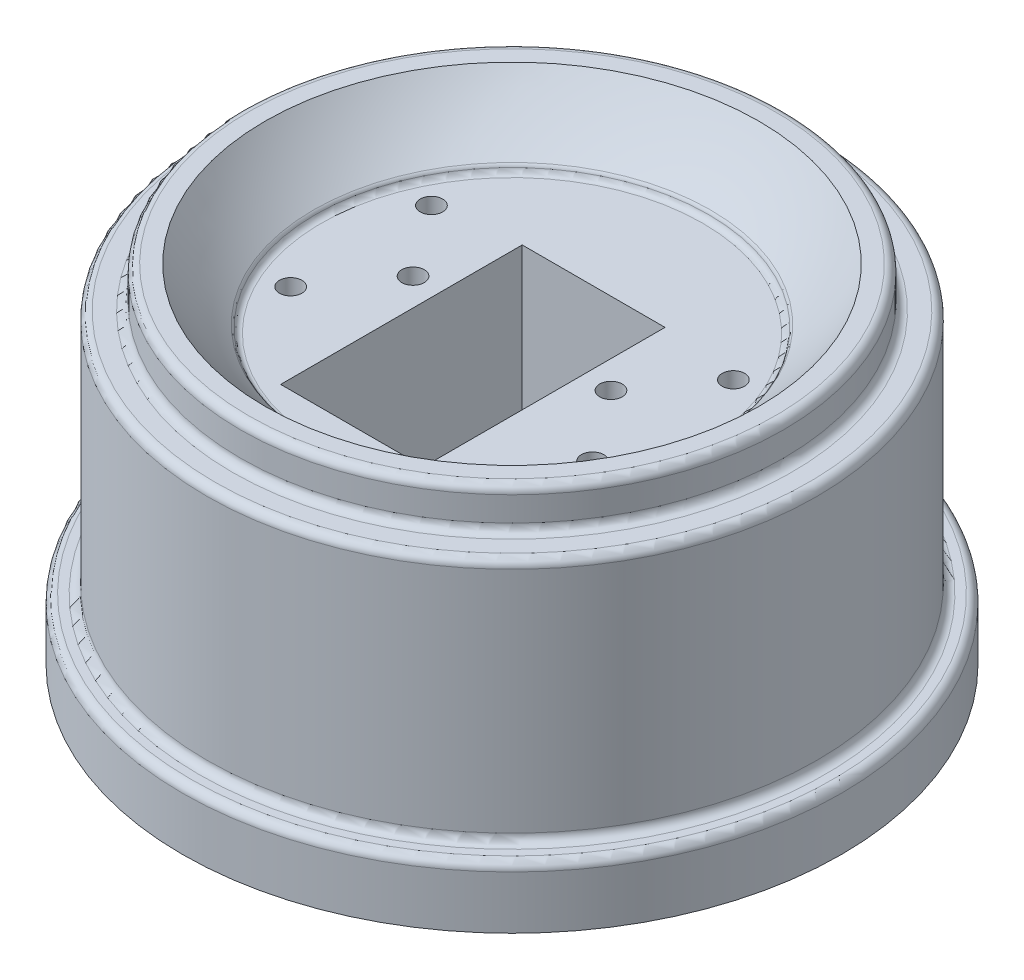
SolidWorks part; units mm, degrees
ref_plane "Front Plane" through (0, 0, 0) normal (0, 0, 1) x (1, 0, 0)
ref_plane "Top Plane" through (0, 0, 0) normal (0, 1, 0) x (1, 0, 0)
ref_plane "Right Plane" through (0, 0, 0) normal (1, 0, 0) x (0, 0, -1)
sketch "Sketch1" plane through (0, 0, 0) normal (0, 0, 1) x (1, 0, 0)
  line L0 (-46.7291, -58.6097) -> (46.7291, -58.6097) construction
  line L1 (0, -58.6097) -> (46.7291, -58.6097)
  line L2 (60.5301, -43.8597) -> (66.5301, -43.8597)
  line L3 (58.5739, -43.8597) -> (-58.5739, -43.8597) construction
  line L4 (0, -128.8597) -> (0, -58.6097)
  line L5 (66.5301, -43.8597) -> (66.5301, -53.8597)
  line L6 (66.5301, -53.8597) -> (74.75, -53.8597)
  line L7 (74.75, -53.8597) -> (74.75, -113.8597)
  line L8 (74.75, -113.8597) -> (80.75, -113.8597)
  line L9 (80.75, -113.8597) -> (80.75, -128.8597)
  line L10 (80.75, -128.8597) -> (0, -128.8597)
  arc A0 (46.7291, -58.6097) -> (48.1773, -57.5003) centre (46.7291, -57.1097) ccw construction
  arc A1 (48.6493, -56.7521) -> (48.1773, -57.5003) centre (49.6256, -57.891) ccw construction
  arc A2 (48.6493, -56.7521) -> (-48.6493, -56.7521) centre (0, 0) ccw construction
  arc A3 (46.7291, -58.6097) -> (48.1773, -57.5003) centre (46.7291, -57.1097) ccw
  arc A4 (48.6493, -56.7521) -> (48.1773, -57.5003) centre (49.6256, -57.891) ccw
  arc A5 (48.6493, -56.7521) -> (60.5301, -43.8597) centre (0, 0) ccw
  point P17 (80.75, -121.3597)
  point P21 (74.75, 0)
  dimension "D1" = 6
  dimension "D2" = 10
  dimension "D3" = 6
  dimension "D4" = 15
  dimension "D5" = 85
revolve "Revolve1" add sketch "Sketch1" angle 360 about L4
fillet "Fillet1" radius 2 3 edges at (0, -113.8597, -80.75) (0, -53.8597, -74.75) (0, -43.8597, -66.5301)
fillet "Fillet2" radius 2 2 edges at (0, -113.8597, -74.75) (0, -53.8597, -66.5301)
sketch "Sketch2" plane through (0, -128.8597, 0) normal (0, -1, 0) x (1, 0, 0)
  line L0 (31, 15.8) -> (-31, 15.8)
  line L1 (-31, -47) -> (31, -47)
  line L2 (-31, -47) -> (-31, 47)
  line L3 (-31, 47) -> (31, 47)
  line L4 (31, -47) -> (31, 47)
  line L5 (-31, -47) -> (31, 47) construction
  line L6 (-31, 47) -> (31, -47) construction
  line L8 (-31, -47) -> (31, -47)
  line L9 (-31, -47) -> (-31, -15.8)
  line L10 (-31, -15.8) -> (31, -15.8)
  line L11 (31, -47) -> (31, -15.8)
  point P0 (0, 0)
  dimension "D1" = 94
  dimension "D2" = 62
  dimension "D3" = 31.2
  dimension "D4" = 31.2
extrude "Cut-Extrude1" cut sketch "Sketch2" against normal blind 33 contours L0 L4 L3 L2 region at (0, -128.8597, 31.4)
sketch "Sketch3" plane through (0, -128.8597, 0) normal (0, -1, 0) x (1, 0, 0)
  line L1 (43, 57) -> (-43, 57)
  line L2 (43, 57) -> (43, -57)
  line L3 (43, -57) -> (-43, -57)
  line L4 (-43, 57) -> (-43, -57)
  line L5 (43, 57) -> (-43, -57) construction
  line L6 (43, -57) -> (-43, 57) construction
  point P0 (0, 0)
  dimension "D1" = 114
  dimension "D2" = 86
extrude "Cut-Extrude2" cut sketch "Sketch3" against normal blind 3
fillet "Fillet3" radius 10 4 edges at (-43, -127.3597, 57) (-43, -127.3597, -57) (43, -127.3597, -57) (43, -127.3597, 57)
extrude "Cut-Extrude3" cut sketch "Sketch2<3>" against normal blind 16 from surface contours L10 L2 L1 L4 region at (0, -128.8597, -31.4) starting at face at (0, -125.8597, 31.4)
sketch "Sketch2<3>" plane through (0, -128.8597, 0) normal (0, -1, 0) x (1, 0, 0) same geometry as "Sketch2"
extrude "Cut-Extrude4" cut sketch "Sketch2<4>" against normal up to surface (33 mm away) contours L2 L10 L4 L0 region at (0, -128.8597, 0) up to face at (0, -95.8597, 31.4)
sketch "Sketch2<4>" plane through (0, -128.8597, 0) normal (0, -1, 0) x (1, 0, 0) same geometry as "Sketch2"
sketch "Sketch6" plane through (0, -95.8597, 0) normal (0, -1, 0) x (-1, 0, 0)
  line L1 (17.5, 20) -> (-17.5, 20)
  line L2 (17.5, 20) -> (17.5, -39.2)
  line L3 (17.5, -39.2) -> (-17.5, -39.2)
  line L4 (-17.5, 20) -> (-17.5, -39.2)
  line L5 (0, 0) -> (0, 20) construction
  dimension "D1" = 39.2
  dimension "D2" = 35
  dimension "D3" = 20
extrude "Cut-Extrude5" cut sketch "Sketch6" against normal up to next and the other way up to next
sketch "Sketch8" plane through (0, -128.8597, 0) normal (0, -1, 0) x (1, 0, 0)
  line L0 (0, 0) -> (0, -58.5739) construction
  line L1 (-24.25, 0) -> (24.25, 0) construction
  line L2 (0, 0) -> (37, 17.2534) construction
  line L3 (0, 0) -> (37, -17.2534) construction
  line L4 (0, 0) -> (-37, -17.2534) construction
  line L5 (0, 0) -> (-37, 17.2534) construction
  line L6 (31, -47) -> (31, 47) construction
  line L7 (31, -47) -> (31, 47) construction
  line L8 (43, 0) -> (31, 0) construction
  line L9 (43, -47) -> (43, 47) construction
  line L10 (17.5, -15.8) -> (17.5, 39.2) construction
  line L11 (17.5, -15.8) -> (17.5, 39.2) construction
  line L12 (31, 0) -> (17.5, 0) construction
  circle A2 centre (0, 0) radius 46.7291 construction
  circle A3 centre (0, 0) radius 46.7291 construction
  point P18 (37, 0)
  point P19 (21.3927, 0)
  point P21 (24.25, 0)
  point P22 (0, 0)
  point P23 (0, 0)
  dimension "D1" = 65
hole_wizard "CBORE for M5 Hex Socket Head Cap Screw" positions "Sketch14" profile "Sketch15" counterbore size "M5" standard "ISO"
sketch "Sketch14" plane through (0, -125.8597, 0) normal (0, -1, 0) x (-1, 0, 0)
  point P0 (-37, -17.2534)
  point P2 (-37, 17.2534)
  point P4 (37, -17.2534)
  point P6 (37, 17.2534)
  point P11 (0, 0)
  point P13 (0, 0)
sketch "Sketch15" plane through (37, -125.8597, 17.2534) normal (1, 0, 0) x (0, 0, -1)
  line L0 (0, 0) -> (0, 81.6524)
  line L1 (0, 81.6524) -> (2.75, 80)
  line L2 (2.75, 80) -> (2.75, 5.4)
  line L3 (2.75, 5.4) -> (5, 5.4)
  line L4 (5, 5.4) -> (5, 0)
  line L5 (5, 0) -> (0, 0)
  line L6 (0, 81.6524) -> (-2.75, 80) construction
  line L7 (0, -6.35) -> (0, 107.95) construction
  dimension "Hole Dia." = 5.5
  dimension "Hole Depth" = 80
  dimension "C'Bore Dia." = 10
  dimension "C'Bore Depth" = 5.4
  dimension "Drill Angle" = 118
hole_wizard "CBORE for M5 Hex Socket Head Cap Screw6" positions "Sketch16" profile "Sketch17" counterbore size "M5" standard "ISO"
sketch "Sketch16" plane through (0, -95.8597, 0) normal (0, -1, 0) x (-1, 0, 0)
  point P0 (-24.25, 0)
  point P2 (24.25, 0)
  point P5 (0, 0)
  point P7 (0, 0)
sketch "Sketch17" plane through (24.25, -95.8597, 0) normal (1, 0, 0) x (0, 0, -1)
  line L0 (0, 0) -> (0, 51.6524)
  line L1 (0, 51.6524) -> (2.75, 50)
  line L2 (2.75, 50) -> (2.75, 5.4)
  line L3 (2.75, 5.4) -> (5, 5.4)
  line L4 (5, 5.4) -> (5, 0)
  line L5 (5, 0) -> (0, 0)
  line L6 (0, 51.6524) -> (-2.75, 50) construction
  line L7 (0, -6.35) -> (0, 107.95) construction
  dimension "Hole Dia." = 5.5
  dimension "Hole Depth" = 50
  dimension "C'Bore Dia." = 10
  dimension "C'Bore Depth" = 5.4
  dimension "Drill Angle" = 118
hole_wizard "M3 Tapped Hole1" positions "Sketch20" profile "Sketch21" tap size "M3" standard "ISO"
sketch "Sketch20" plane through (0, -125.8597, 0) normal (0, -1, 0) x (-1, 0, 0)
  point P0 (37, 37)
  point P3 (37, -37)
  point P6 (-37, -37)
  point P9 (-37, 37)
sketch "Sketch21" plane through (-37, -125.8597, -37) normal (1, 0, 0) x (0, 0, -1)
  line L0 (0, 0) -> (0, 20.7511)
  line L1 (0, 20.7511) -> (1.25, 20)
  line L2 (1.25, 20) -> (1.25, 0)
  line L5 (1.25, 0) -> (0, 0)
  line L10 (0, 20.7511) -> (-1.25, 20) construction
  line L11 (0, -6.35) -> (0, 107.95) construction
  dimension "Tap Drill Dia." = 2.5
  dimension "Tap Drill Depth" = 20
  dimension "Drill Angle" = 118
hole_wizard "M4 Tapped Hole1" positions "Sketch22" profile "Sketch24" tap size "M4" standard "ISO"
sketch "Sketch22" plane through (0, -95.8597, 0) normal (0, -1, 0) x (-1, 0, 0)
  point P0 (22.35, -31.4)
  point P3 (-22.35, -31.4)
sketch "Sketch24" plane through (-22.35, -95.8597, 31.4) normal (1, 0, 0) x (0, 0, -1)
  line L0 (0, 0) -> (0, 10.9914)
  line L1 (0, 10.9914) -> (1.65, 10)
  line L2 (1.65, 10) -> (1.65, 0)
  line L5 (1.65, 0) -> (0, 0)
  line L10 (0, 10.9914) -> (-1.65, 10) construction
  line L11 (0, -6.35) -> (0, 107.95) construction
  dimension "Tap Drill Dia." = 3.3
  dimension "Tap Drill Depth" = 10
  dimension "Drill Angle" = 118
hole_wizard "M3 Tapped Hole2" positions "Sketch25" profile "Sketch26" tap size "M3" standard "ISO"
sketch "Sketch25" plane through (0, -110.8597, 0) normal (0, -1, 0) x (-1, 0, 0)
  point P0 (7.2, 31.4)
  point P3 (0, 31.4)
  point P6 (-7.2, 31.4)
sketch "Sketch26" plane through (-7.2, -110.8597, -31.4) normal (1, 0, 0) x (0, 0, -1)
  line L0 (0, 0) -> (0, 16.7511)
  line L1 (0, 16.7511) -> (1.25, 16)
  line L2 (1.25, 16) -> (1.25, 1.75)
  line L3 (1.25, 1.75) -> (3, 0)
  line L4 (3, 0) -> (0, 0)
  line L5 (-1.25, 1.75) -> (-3, 0) construction
  line L6 (0, 16.7511) -> (-1.25, 16) construction
  line L7 (0, -6.35) -> (0, 107.95) construction
  dimension "Tap Drill Dia." = 2.5
  dimension "Tap Drill Depth" = 16
  dimension "Near C'Sink Dia." = 6
  dimension "Near C'Sink Angle" = 90
  dimension "Drill Angle" = 118
